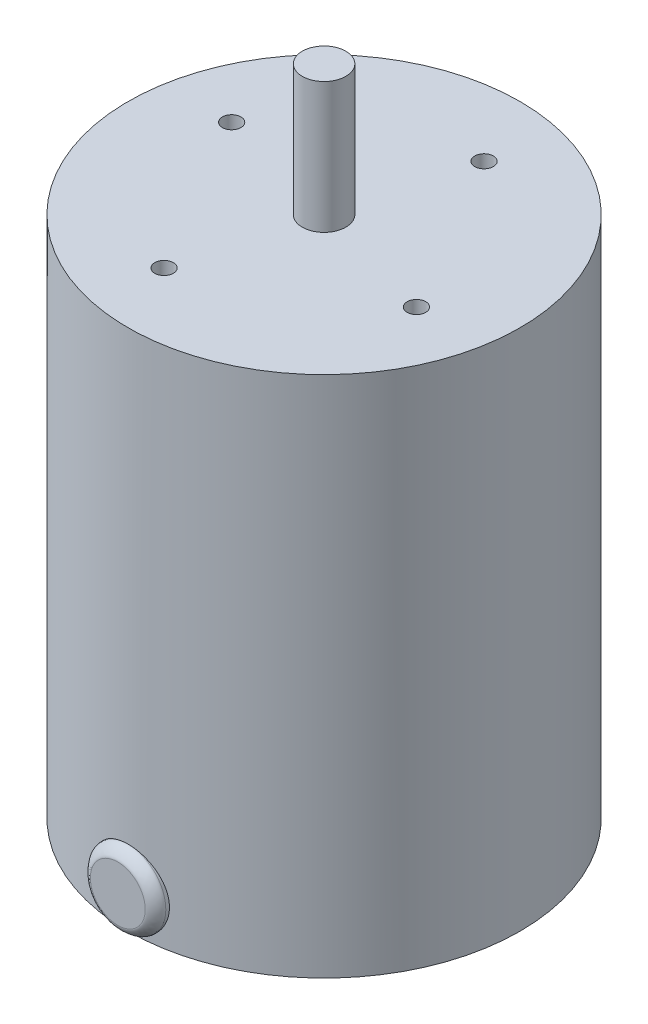
SolidWorks part; units mm, degrees
ref_plane "Front" through (0, 0, 0) normal (0, 0, 1) x (1, 0, 0)
ref_plane "Top" through (0, 0, 0) normal (0, 1, 0) x (1, 0, 0)
ref_plane "Right" through (0, 0, 0) normal (1, 0, 0) x (0, 0, -1)
sketch "Sketch1" plane through (0, 0, 0) normal (0, 0, 1) x (1, 0, 0)
  line L0 (0, 38.1) -> (0, -38.1)
  line L1 (0, -38.1) -> (28.575, -38.1)
  line L2 (28.575, -38.1) -> (28.575, 38.1)
  line L3 (28.575, 38.1) -> (3.175, 38.1)
  line L4 (3.175, 38.1) -> (3.175, 57.15)
  line L5 (3.175, 57.15) -> (0, 57.15)
  line L6 (0, 57.15) -> (0, 38.1)
  line L7 (0, 0) -> (0, 24.0027) construction
  point P2 (0, 0)
  dimension "D1" = 76.2
  dimension "D2" = 19.05
  dimension "D3" = 6.35
  dimension "D4" = 57.15
revolve "Revolve1" add sketch "Sketch1" angle 360 about L7
ref_plane "Plane1" through (0, 0, 28.575) normal (0, 0, 1) x (1, 0, 0)
sketch "Sketch2" plane through (0, 0, 28.575) normal (0, 0, 1) x (1, 0, 0)
  line L0 (-28.575, -38.1) -> (28.575, -38.1) construction
  circle A0 centre (0, -32.6) radius 5.5
  point P4 (0, 0)
  dimension "D1" = 11
extrude "Boss-Extrude1" add sketch "Sketch2" along normal mid plane 3
hole_wizard "#6-32 Tapped Hole1" positions "Sketch3" profile "Sketch5" tap size "#6-32" standard "ANSI Inch"
sketch "Sketch3" plane through (0, 38.1, 0) normal (0, 1, 0) x (1, 0, 0)
  line L0 (0, 0) -> (0, 37.8714)
  line L3 (4.9305, 18.4009) -> (0, 0)
  circle A0 centre (0, 0) radius 19.05
  point P0 (4.9305, 18.4009)
  dimension "D1" = 38.1
  dimension "D2" = 15
sketch "Sketch5" plane through (4.9305, 38.1, -18.4009) normal (1, 0, 0) x (0, 0, 1)
  line L0 (0, 0) -> (0, 6.8127)
  line L1 (0, 6.8127) -> (1.3525, 6)
  line L2 (1.3525, 6) -> (1.3525, 0)
  line L5 (1.3525, 0) -> (0, 0)
  line L10 (0, 6.8127) -> (-1.3526, 6) construction
  line L11 (0, -6.35) -> (0, 107.95) construction
  dimension "Tap Drill Dia." = 2.7051
  dimension "Tap Drill Depth" = 6
  dimension "Drill Angle" = 118
cosmetic thread "Hole Thread1" parameters "D1"=6, "D2"=3.5052
pattern_circular "CirPattern1" count 4 over 360 about axis through (0, 0, 0) along (0, -1, 0) of "#6-32 Tapped Hole1"
fillet "Fillet2" radius 1.5 1 edges at (5.5, -32.6, 30.075) conic rho 0.25
